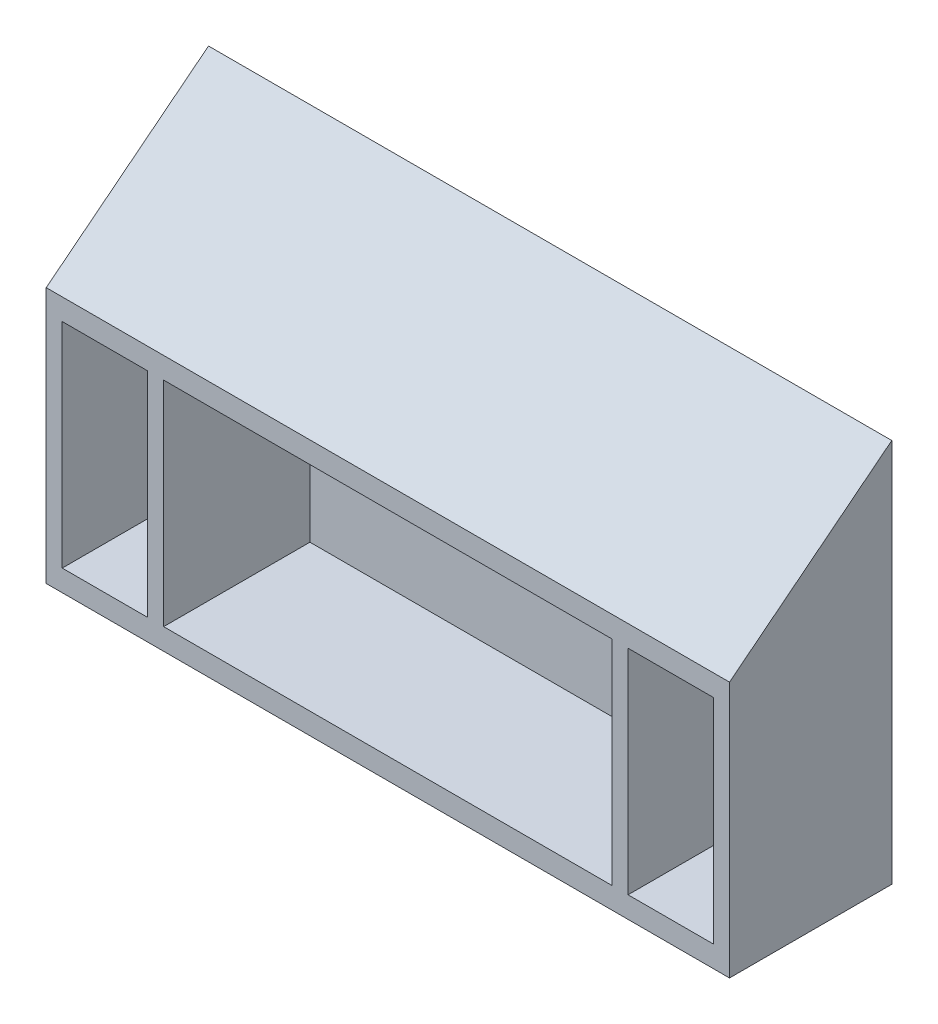
SolidWorks part; units mm, degrees
ref_plane "Front Plane" through (0, 0, 0) normal (0, 0, 1) x (1, 0, 0)
ref_plane "Top Plane" through (0, 0, 0) normal (0, 1, 0) x (1, 0, 0)
ref_plane "Right Plane" through (0, 0, 0) normal (1, 0, 0) x (0, 0, -1)
sketch "Sketch1" plane through (0, 0, 0) normal (0, 0, 1) x (1, 0, 0)
  line L1 (-101.6, -38.1) -> (101.6, -38.1)
  line L2 (-101.6, -38.1) -> (-101.6, 38.1)
  line L3 (-101.6, 38.1) -> (101.6, 38.1)
  line L4 (101.6, -38.1) -> (101.6, 38.1)
  line L5 (-101.6, -38.1) -> (101.6, 38.1) construction
  line L6 (-101.6, 38.1) -> (101.6, -38.1) construction
  line L7 (-96.8375, 31.75) -> (-71.4375, 31.75)
  line L8 (-96.8375, 31.75) -> (-96.8375, -31.75)
  line L9 (-96.8375, -31.75) -> (-71.4375, -31.75)
  line L10 (-71.4375, 31.75) -> (-71.4375, -31.75)
  line L11 (-96.8375, 31.75) -> (-71.4375, -31.75) construction
  line L12 (-96.8375, -31.75) -> (-71.4375, 31.75) construction
  line L13 (71.4375, 31.75) -> (96.8375, 31.75)
  line L14 (71.4375, 31.75) -> (71.4375, -31.75)
  line L15 (71.4375, -31.75) -> (96.8375, -31.75)
  line L16 (96.8375, 31.75) -> (96.8375, -31.75)
  line L17 (71.4375, 31.75) -> (96.8375, -31.75) construction
  line L18 (71.4375, -31.75) -> (96.8375, 31.75) construction
  point P0 (0, 0)
  point P6 (-84.1375, 0)
  point P11 (84.1375, 0)
  dimension "D1" = 203.2
  dimension "D2" = 76.2
  dimension "D3" = 4.7625
  dimension "D4" = 6.35
  dimension "D5" = 63.5
  dimension "D6" = 25.4
  dimension "D7" = 25.4
  dimension "D8" = 63.5
  dimension "D9" = 4.7625
  dimension "D10" = 6.35
extrude "Boss-Extrude1" add sketch "Sketch1" along normal blind 48.26
sketch "Sketch2" plane through (0, 0, 48.26) normal (0, 0, 1) x (1, 0, 0)
  line L0 (101.6, 38.1) -> (-101.6, 38.1) construction
  line L1 (-66.675, -31.75) -> (66.675, -31.75)
  line L2 (-66.675, -31.75) -> (-66.675, 31.75)
  line L3 (-66.675, 31.75) -> (66.675, 31.75)
  line L4 (66.675, -31.75) -> (66.675, 31.75)
  line L5 (-66.675, -31.75) -> (66.675, 31.75) construction
  line L6 (-66.675, 31.75) -> (66.675, -31.75) construction
  line L8 (-71.4375, -31.75) -> (-71.4375, 31.75) construction
  point P1 (0, 0)
  dimension "D1" = 6.35
  dimension "D2" = 4.7625
extrude "Cut-Extrude1" cut sketch "Sketch2" against normal blind 43.4975
sketch "Sketch3" plane through (101.6, 0, 0) normal (1, 0, 0) x (0, 0, -1)
  line L0 (-48.26, 38.1) -> (0, 76.2)
  line L1 (0, 76.2) -> (0, 38.1)
  line L2 (-48.26, 38.1) -> (0, 38.1)
  dimension "D1" = 38.1
extrude "Boss-Extrude3" add sketch "Sketch3" against normal blind 203.2
